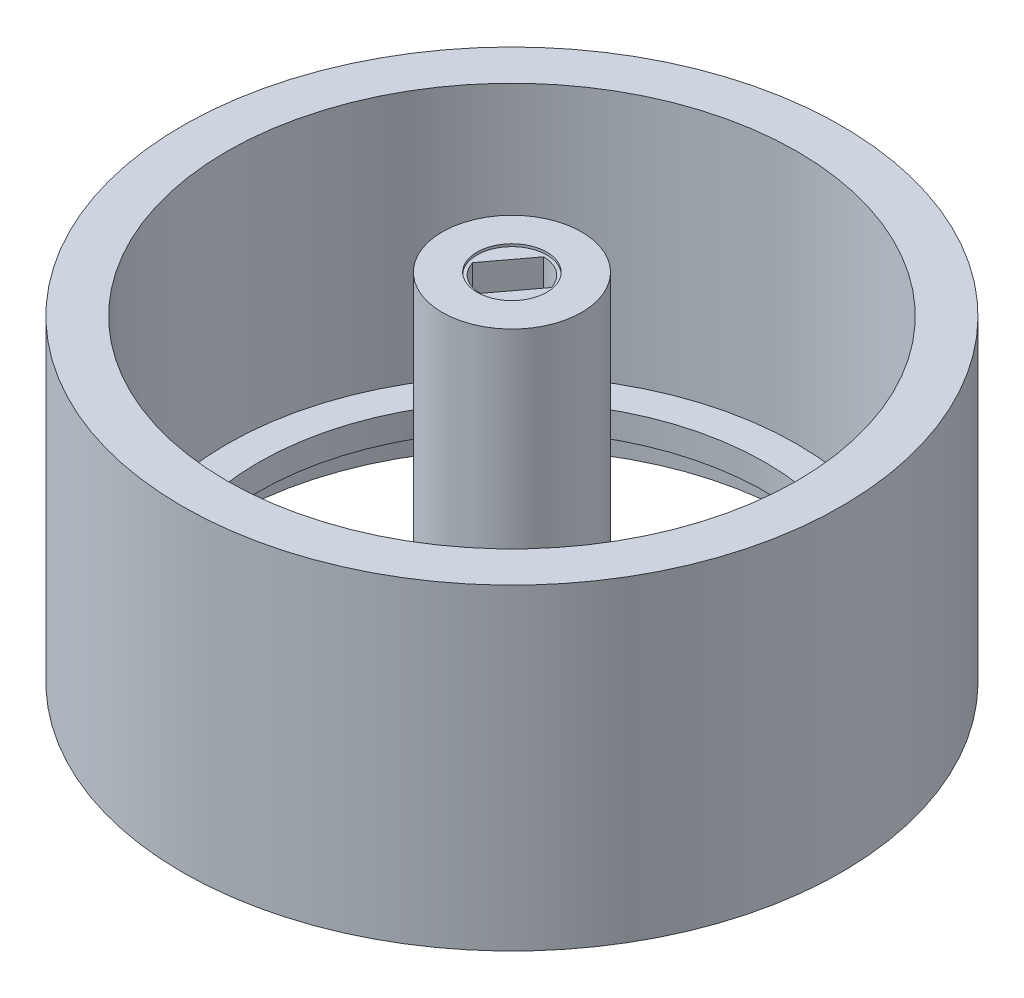
SolidWorks part; units mm, degrees
ref_plane "Front Plane" through (0, 0, 0) normal (0, 0, 1) x (1, 0, 0)
ref_plane "Top Plane" through (0, 0, 0) normal (0, 1, 0) x (1, 0, 0)
ref_plane "Right Plane" through (0, 0, 0) normal (1, 0, 0) x (0, 0, -1)
sketch "Sketch1" plane through (0, 0, 0) normal (0, 1, 0) x (1, 0, 0)
  circle A0 centre (0, 0) radius 22.5
  circle A1 centre (0, 0) radius 26
  dimension "D1" = 52
  dimension "D2" = 45
extrude "Boss-Extrude1" add sketch "Sketch1" along normal blind 25
ref_plane "Plane1" through (0, 5, 0) normal (0, 1, 0) x (1, 0, 0)
sketch "Sketch3" plane through (0, 5, 0) normal (0, 1, 0) x (1, 0, 0)
  circle A0 centre (0, 0) radius 22.5
  circle A1 centre (0, 0) radius 20
  dimension "D1" = 40
  dimension "D2" = 45
extrude "Boss-Extrude2" add sketch "Sketch3" against normal blind 2
sketch "Sketch4" plane through (0, 3, 0) normal (0, -1, 0) x (1, 0, 0)
  line L0 (8.6784, -20.759) -> (0.8026, -10.9707) construction
  line L1 (13.8563, -17.7272) -> (9.1734, -6.0704) construction
  line L2 (22.4247, 1.8388) -> (10.6818, -2.6268) construction
  line L3 (21.1414, 7.7001) -> (8.608, 6.8485) construction
  line L4 (-17.0612, -14.6686) -> (-10.1857, -4.1535) construction
  line L5 (-12.5777, -18.6561) -> (-2.9386, -10.6002) construction
  line L6 (-19.2228, 11.6933) -> (-7.0978, 8.4037) construction
  line L7 (-21.6298, 6.197) -> (-10.9895, -0.4809) construction
  line L8 (5.1808, 21.8954) -> (5.7991, 9.3472) construction
  line L9 (-0.7902, 22.4861) -> (-3.8533, 10.303) construction
  line L10 (0, 0) -> (10.6818, -2.6268) construction
  line L11 (0, 0) -> (0.8026, -10.9707) construction
  arc A2 (8.6784, -20.759) -> (13.8563, -17.7272) centre (0, 0) ccw
  arc A3 (22.4247, 1.8388) -> (21.1414, 7.7001) centre (0, 0) ccw
  arc A6 (-17.0612, -14.6686) -> (-12.5777, -18.6561) centre (0, 0) ccw
  arc A8 (-19.2228, 11.6933) -> (-21.6298, 6.197) centre (0, 0) ccw
  arc A10 (5.1808, 21.8954) -> (-0.7902, 22.4861) centre (0, 0) ccw
  circle A11 centre (0, 0.4917) radius 2.5
  spline S0 degree 3 poles (-0.7902, 22.4861) (-1.8113, 18.4251) (-2.8323, 14.364) (-3.8533, 10.303) (-3.9552, 9.8979) (-4.1589, 9.0877) (-5.8883, 8.0756) (-6.6946, 8.2943) (-7.0978, 8.4037) (-11.1394, 9.5002) (-15.1811, 10.5968) (-19.2228, 11.6933) knots 0 0 0 0 0.25002 0.25002 0.25002 0.274961 0.299902 0.324843 0.324843 0.324843 0.574886 0.574886 0.574886 0.574886
  spline S1 degree 3 poles (-17.0612, -14.6686) (-14.7693, -11.1635) (-12.4775, -7.6585) (-10.1857, -4.1535) (-9.9571, -3.8039) (-9.4999, -3.1046) (-9.9281, -1.1471) (-10.6357, -0.703) (-10.9895, -0.4809) (-14.5362, 1.7451) (-18.083, 3.9711) (-21.6298, 6.197) knots 0 0 0 0 0.250042 0.250042 0.250042 0.274983 0.299924 0.324865 0.324865 0.324865 0.574886 0.574886 0.574886 0.574886
  spline S2 degree 3 poles (21.1414, 7.7001) (16.9636, 7.4163) (12.7858, 7.1324) (8.608, 6.8485) (8.1912, 6.8202) (7.3577, 6.7636) (5.8607, 8.0956) (5.8196, 8.93) (5.7991, 9.3472) (5.593, 13.53) (5.3869, 17.7127) (5.1808, 21.8954) knots 0 0 0 0 0.25002 0.25002 0.25002 0.274961 0.299902 0.324843 0.324843 0.324843 0.574886 0.574886 0.574886 0.574886
  spline S3 degree 3 poles (13.8563, -17.7272) (12.2953, -13.8416) (10.7343, -9.956) (9.1734, -6.0704) (9.0176, -5.6828) (8.7062, -4.9075) (9.5104, -3.0722) (10.2913, -2.7752) (10.6818, -2.6268) (14.5961, -1.1382) (18.5104, 0.3503) (22.4247, 1.8388) knots 0 0 0 0 0.25002 0.25002 0.25002 0.274961 0.299902 0.324843 0.324843 0.324843 0.574886 0.574886 0.574886 0.574886
  spline S4 degree 3 poles (8.6784, -20.759) (6.0532, -17.4962) (3.4279, -14.2334) (0.8026, -10.9707) (0.5408, -10.6452) (0.0171, -9.9943) (-1.977, -9.7966) (-2.618, -10.3324) (-2.9386, -10.6002) (-6.1516, -13.2855) (-9.3646, -15.9708) (-12.5777, -18.6561) knots 0 0 0 0 0.250042 0.250042 0.250042 0.274983 0.299924 0.324865 0.324865 0.324865 0.574886 0.574886 0.574886 0.574886
  dimension "D2" = 45
  dimension "D5" = 5
  dimension "D4" = 72
  dimension "D3" = 5
extrude "Boss-Extrude3" add sketch "Sketch4" along normal blind 2
sketch "Sketch5" plane through (0, 3, 0) normal (0, 1, 0) x (1, 0, 0)
  circle A0 centre (0, 0) radius 5.5
  dimension "D1" = 11
extrude "Boss-Extrude4" add sketch "Sketch5" along normal blind 25 separate body
sketch "Sketch6" plane through (0, 28, 0) normal (0, 1, 0) x (1, 0, 0)
  line L1 (-2.4, -0.7) -> (0, 2.5)
  line L2 (2.4, 0.7) -> (0, -2.5)
  arc A0 (-2.4, -0.7) -> (0, -2.5) centre (0, 0) ccw
  arc A1 (2.4, 0.7) -> (0, 2.5) centre (0, 0) ccw
  dimension "D1" = 5
  dimension "D2" = 4
extrude "Cut-Extrude1" cut sketch "Sketch6" against normal blind 20
sketch "Sketch7" plane through (0, 1, 0) normal (0, -1, 0) x (1, 0, 0)
  circle A0 centre (0, 0) radius 9
  dimension "D1" = 18
extrude "Cut-Extrude2" cut sketch "Sketch7" against normal blind 1
fillet "Fillet5" radius 5 1 edges at (0, 1, -9)
sketch "Sketch8" plane through (0, 2, 0) normal (0, -1, 0) x (1, 0, 0)
  circle A0 centre (0, 0) radius 5.0114
extrude "Boss-Extrude5" add sketch "Sketch8" along normal blind 2
fillet "Fillet6" radius 1 1 edges at (0, 0, -5.0114)
sketch "Sketch9" plane through (0, 28, 0) normal (0, 1, 0) x (1, 0, 0)
  circle A0 centre (0, 0) radius 2.75
  dimension "D1" = 5.5
extrude "Cut-Extrude3" cut sketch "Sketch9" against normal blind 0.2
